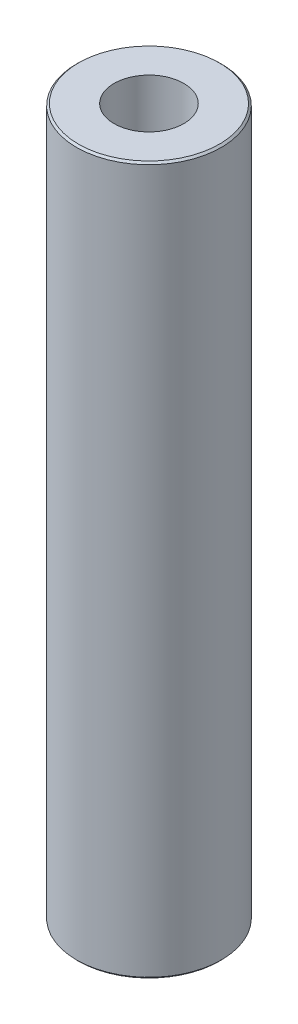
SolidWorks part; units mm, degrees
ref_plane "Front Plane" through (0, 0, 0) normal (0, 0, 1) x (1, 0, 0)
ref_plane "Top Plane" through (0, 0, 0) normal (0, 1, 0) x (1, 0, 0)
ref_plane "Right Plane" through (0, 0, 0) normal (1, 0, 0) x (0, 0, -1)
sketch "Sketch1" plane through (0, 0, 0) normal (0, 1, 0) x (1, 0, 0)
  circle A0 centre (0, 0) radius 57.5
  dimension "SHAFT_OD" = 115
extrude "Boss-Extrude1" add sketch "Sketch1" along normal blind 561.934
sketch "Sketch2" plane through (0, 0, 0) normal (0, 1, 0) x (1, 0, 0)
  circle A0 centre (0, 0) radius 27.7017
  dimension "BORE_D" = 55.4034
extrude "Cut-Extrude1" cut sketch "Sketch2" along normal through all
chamfer "Chamfer1" distance 1.467 angle 46.525 2 edges at (0, 561.934, 57.5) (0, 0, 57.5) first distance on face at (0, 561.934, 57.5) first distance on face at (0, 0, 27.7017)
